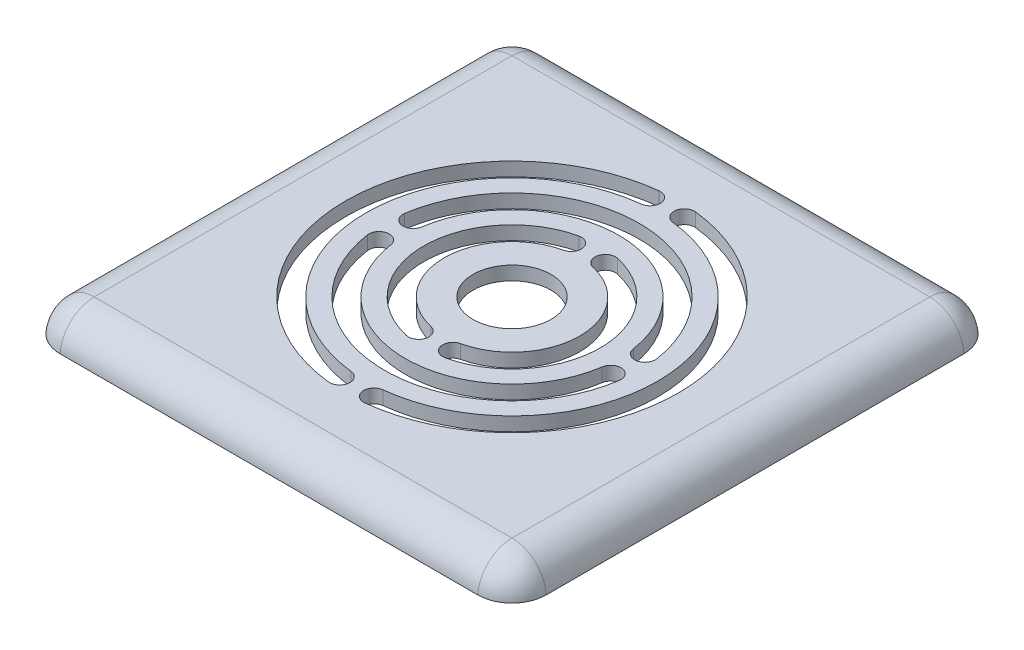
SolidWorks part; units mm, degrees
ref_plane "Спереди" through (0, 0, 0) normal (0, 0, 1) x (1, 0, 0)
ref_plane "Сверху" through (0, 0, 0) normal (0, 1, 0) x (1, 0, 0)
ref_plane "Справа" through (0, 0, 0) normal (1, 0, 0) x (0, 0, -1)
sketch "Эскиз1" plane through (0, 0, 0) normal (0, 1, 0) x (1, 0, 0)
  line L1 (-30.5, 35.5) -> (30.5, 35.5)
  line L2 (-35.5, 30.5) -> (-35.5, -30.5)
  line L3 (-30.5, -35.5) -> (30.5, -35.5)
  line L4 (35.5, 30.5) -> (35.5, -30.5)
  line L5 (-35.5, 35.5) -> (35.5, -35.5) construction
  line L6 (-35.5, -35.5) -> (35.5, 35.5) construction
  circle A0 centre (0, 0) radius 28.5 construction
  arc A1 (-30.5, -35.5) -> (-35.5, -30.5) centre (-30.5, -30.5) cw
  arc A2 (30.5, -35.5) -> (35.5, -30.5) centre (30.5, -30.5) ccw
  arc A3 (35.5, 30.5) -> (30.5, 35.5) centre (30.5, 30.5) ccw
  arc A4 (-30.5, 35.5) -> (-35.5, 30.5) centre (-30.5, 30.5) ccw
  dimension "D1" = 57
  dimension "D3" = 5
  dimension "D2" = 71
ref_plane "Плоскость1" through (0, 4.7, 0) normal (0, 1, 0) x (1, 0, 0)
extrude "Бобышка-Вытянуть1" add sketch "Эскиз1" along normal blind 4.7
fillet "Скругление1" radius 5 8 edges at (-34.0355, 4.7, 34.0355) (-35.5, 4.7, 0) (-34.0355, 4.7, -34.0355) (0, 4.7, -35.5) (34.0355, 4.7, -34.0355) (35.5, 4.7, 0) (34.0355, 4.7, 34.0355) (0, 4.7, 35.5)
sketch "Эскиз2" plane through (0, 0, 0) normal (0, 1, 0) x (1, 0, 0)
  circle A0 centre (0, 0) radius 29.5
  circle A1 centre (0, 0) radius 28.5 construction
  dimension "D1" = 1
extrude "Вырез-Вытянуть1" cut sketch "Эскиз2" along normal offset from surface (2.7 mm away) 2 up to face at (0, 4.7, 0)
sketch "Эскиз3" plane through (0, 4.7, 0) normal (0, 1, 0) x (1, 0, 0)
  line L0 (0, 22.8) -> (0, -22.8) construction
  line L1 (-22.8, 0) -> (22.8, 0) construction
  line L2 (-35.5, 35.5) -> (35.5, -35.5) construction
  line L3 (-35.5, -35.5) -> (35.5, 35.5) construction
  circle A0 centre (0, 0) radius 5.7
  circle A1 centre (0, 0) radius 11.4 construction
  circle A2 centre (0, 0) radius 17.1 construction
  circle A3 centre (0, 0) radius 22.8 construction
  arc A4 (2.5, 11.1225) -> (2.5, -11.1225) centre (0, 0) cw construction
  arc A5 (2.8289, -12.586) -> (2.8289, 12.586) centre (0, 0) ccw
  arc A6 (2.1711, -9.659) -> (2.1711, 9.659) centre (0, 0) ccw
  arc A7 (2.1711, -9.659) -> (2.8289, -12.586) centre (2.5, -11.1225) ccw
  arc A8 (2.8289, 12.586) -> (2.1711, 9.659) centre (2.5, 11.1225) ccw
  arc A9 (-2.5, 11.1225) -> (-2.5, -11.1225) centre (0, 0) ccw construction
  arc A10 (-2.8289, 12.586) -> (-2.8289, -12.586) centre (0, 0) ccw
  arc A11 (-2.1711, 9.659) -> (-2.1711, -9.659) centre (0, 0) ccw
  arc A12 (-2.1711, 9.659) -> (-2.8289, 12.586) centre (-2.5, 11.1225) ccw
  arc A13 (-2.8289, -12.586) -> (-2.1711, -9.659) centre (-2.5, -11.1225) ccw
  arc A14 (-16.9163, 2.5) -> (16.9163, 2.5) centre (0, 0) cw construction
  arc A15 (18.4001, 2.7193) -> (-18.4001, 2.7193) centre (0, 0) ccw
  arc A16 (15.4324, 2.2807) -> (-15.4324, 2.2807) centre (0, 0) ccw
  arc A17 (15.4324, 2.2807) -> (18.4001, 2.7193) centre (16.9163, 2.5) ccw
  arc A18 (-18.4001, 2.7193) -> (-15.4324, 2.2807) centre (-16.9163, 2.5) ccw
  arc A19 (-16.9163, -2.5) -> (16.9163, -2.5) centre (0, 0) ccw construction
  arc A20 (-18.4001, -2.7193) -> (18.4001, -2.7193) centre (0, 0) ccw
  arc A21 (-15.4324, -2.2807) -> (15.4324, -2.2807) centre (0, 0) ccw
  arc A22 (-15.4324, -2.2807) -> (-18.4001, -2.7193) centre (-16.9163, -2.5) ccw
  arc A23 (18.4001, -2.7193) -> (15.4324, -2.2807) centre (16.9163, -2.5) ccw
  arc A24 (-2.5, 22.6625) -> (-2.5, -22.6625) centre (0, 0) ccw construction
  arc A25 (-2.6645, 24.1535) -> (-2.6645, -24.1535) centre (0, 0) ccw
  arc A26 (-2.3355, 21.1716) -> (-2.3355, -21.1716) centre (0, 0) ccw
  arc A27 (-2.3355, 21.1716) -> (-2.6645, 24.1535) centre (-2.5, 22.6625) ccw
  arc A28 (-2.6645, -24.1535) -> (-2.3355, -21.1716) centre (-2.5, -22.6625) ccw
  arc A29 (2.5, -22.6625) -> (2.5, 22.6625) centre (0, 0) ccw construction
  arc A30 (2.6645, -24.1535) -> (2.6645, 24.1535) centre (0, 0) ccw
  arc A31 (2.3355, -21.1716) -> (2.3355, 21.1716) centre (0, 0) ccw
  arc A32 (2.3355, -21.1716) -> (2.6645, -24.1535) centre (2.5, -22.6625) ccw
  arc A33 (2.6645, 24.1535) -> (2.3355, 21.1716) centre (2.5, 22.6625) ccw
  point P12 (11.4, 0)
  point P22 (-11.4, 0)
  point P30 (0, 17.1)
  point P40 (0, -17.1)
  point P48 (-22.8, 0)
  point P56 (22.8, 0)
  point P61 (0, 0)
  point P62 (0, 0)
  point P63 (0, 0)
  point P64 (0, 0)
  point P65 (0, 0)
  point P66 (0, 0)
  point P67 (16.3753, 4.9253)
  point P68 (16.3753, -4.9253)
  point P69 (16.3753, -4.9253)
  point P70 (-16.6448, -3.9192)
  point P71 (0, 0)
  point P72 (0, 0)
  point P73 (16.3753, -4.9253)
  point P74 (16.3753, -4.9253)
  point P75 (16.3753, -4.9253)
  point P76 (-15.8186, 6.4947)
  point P77 (15.5454, 7.1239)
  point P78 (15.5454, -6.1666)
  point P79 (0, 0)
  point P80 (0, 0)
  point P81 (16.4249, -4.7575)
  dimension "D1" = 11.4
  dimension "D2" = 22.8
  dimension "D3" = 34.2
  dimension "D4" = 45.6
  dimension "D5" = 1.5
  dimension "D6" = 5
  dimension "D7" = 5
  dimension "D8" = 5
  dimension "D9" = 5
  dimension "D10" = 5
  dimension "D11" = 5
extrude "Вырез-Вытянуть2" cut sketch "Эскиз3" against normal through all
